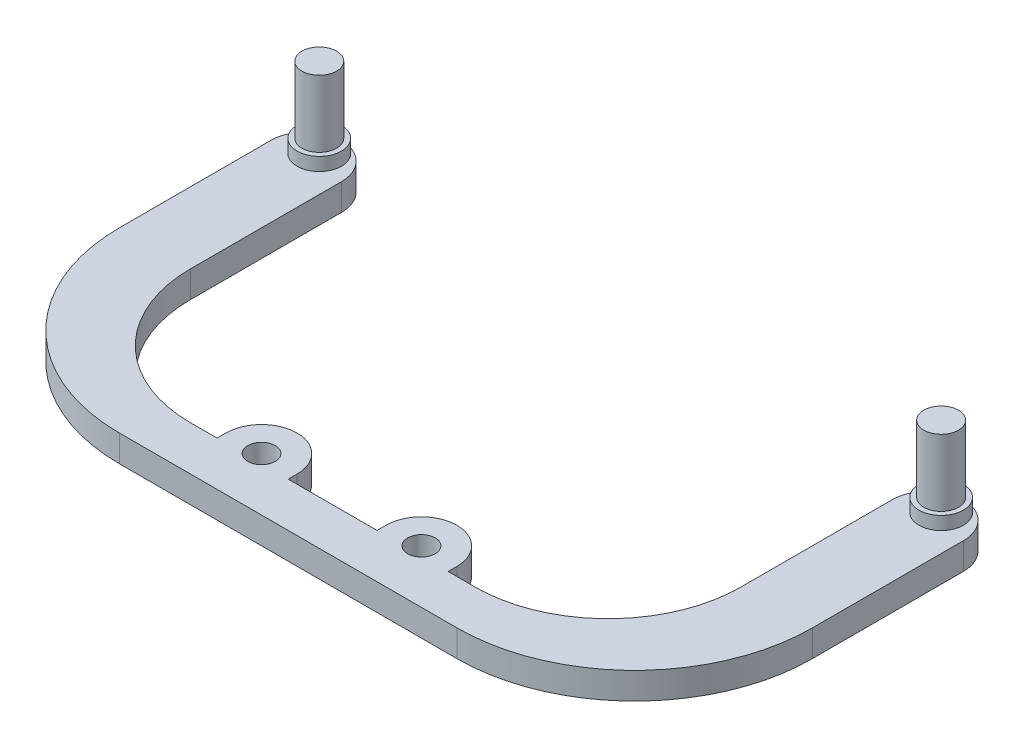
SolidWorks part; units mm, degrees
ref_plane "前视基准面" through (0, 0, 0) normal (0, 0, 1) x (1, 0, 0)
ref_plane "上视基准面" through (0, 0, 0) normal (0, 1, 0) x (1, 0, 0)
ref_plane "右视基准面" through (0, 0, 0) normal (1, 0, 0) x (0, 0, -1)
other "Configuration Table"
sketch "草图1" plane through (0, 0, 0) normal (0, 1, 0) x (1, 0, 0)
  line L0 (-39, 37) -> (-31, 37)
  line L1 (-31, 37) -> (-31, 0)
  line L2 (-31, 0) -> (-13, 0)
  line L3 (-13, 0) -> (-13, 5)
  line L4 (-13, 5) -> (-5, 5)
  line L5 (-5, 5) -> (-5, 0)
  line L6 (-5, 0) -> (0, 0)
  line L7 (0, 0) -> (0, -5)
  line L8 (0, -5) -> (-39, -5)
  line L9 (-39, -5) -> (-39, 37)
  point P14 (-35, 37)
  point P15 (-9, 5)
  dimension "D1" = 8
  dimension "D2" = 8
  dimension "D3" = 42
  dimension "D4" = 5
  dimension "D5" = 5
  dimension "D6" = 35
  dimension "D7" = 9
extrude "凸台-拉伸1" add sketch "草图1" along normal blind 3
sketch "草图2" plane through (0, 3, 0) normal (0, 1, 0) x (1, 0, 0)
  line L1 (-5, 5) -> (-13, 5) construction
  circle A1 centre (-9, 1) radius 1.55
  dimension "D2" = 4
  dimension "D4" = 3.1
  dimension "D6" = 9
extrude "切除-拉伸1" cut sketch "草图2" against normal blind 3
sketch "草图3" plane through (0, 3, 0) normal (0, 1, 0) x (1, 0, 0)
  circle A0 centre (-35, 33.5) radius 1.95
  circle A1 centre (-9, 1) radius 1.55 construction
  dimension "D1" = 35
  dimension "D2" = 32.5
  dimension "D3" = 3.9
extrude "凸台-拉伸2" add sketch "草图3" along normal blind 9
mirror "镜向1" about plane through (0, 3, 0) normal (-1, 0, 0) of "切除-拉伸1", "凸台-拉伸2", "凸台-拉伸1"
fillet "圆角4" 2 edges at (-13, 1.5, -5) (-5, 1.5, -5) type full round first side face at (-13, 1.5, -2.5) second side face at (-5, 1.5, -2.5) middle face at (-9, 1.5, -5)
fillet "圆角5" 2 edges at (13, 1.5, -5) (5, 1.5, -5) type full round first side face at (13, 1.5, -2.5) second side face at (5, 1.5, -2.5) middle face at (9, 1.5, -5)
sketch "草图4" plane through (0, 3, 0) normal (0, 1, 0) x (1, 0, 0)
  circle A0 centre (-35, 33.5) radius 2.5
  dimension "D1" = 5
extrude "凸台-拉伸3" add sketch "草图4" along normal blind 1.48
mirror "镜向2" about plane through (0, 0, 0) normal (1, 0, 0) of "凸台-拉伸3"
fillet "圆角6" radius 15 2 edges at (31, 1.5, 0) (-31, 1.5, 0)
fillet "圆角7" radius 20 2 edges at (39, 1.5, 5) (-39, 1.5, 5)
sketch "草图5" plane through (0, 3, 0) normal (0, 1, 0) x (1, 0, 0)
  line L0 (-39, 37) -> (-39, 15) construction
  line L1 (-31, 15) -> (-31, 37) construction
  line L2 (-39, 32) -> (-39, 37)
  line L3 (-39, 37) -> (-31, 37)
  line L4 (-31, 37) -> (-31, 32)
  arc A0 (-31, 32) -> (-39, 32) centre (-35, 32) ccw
  circle A1 centre (-35, 33.5) radius 2.5 construction
extrude "切除-拉伸2" cut sketch "草图5" against normal through all
mirror "镜向3" about plane through (0, 0, 0) normal (1, 0, 0) of "切除-拉伸2"
